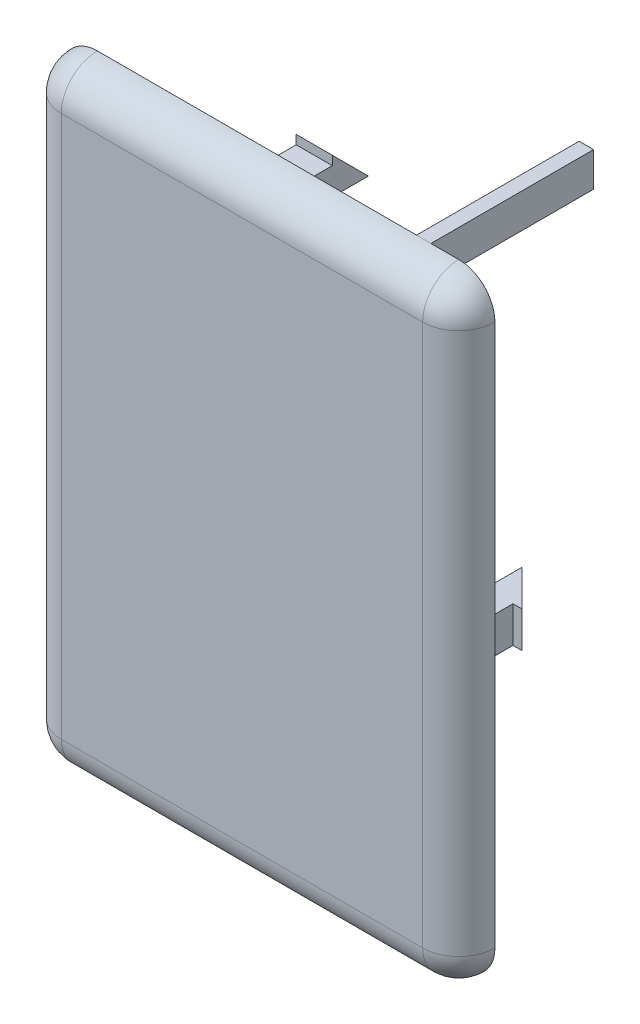
SolidWorks part; units mm, degrees
other "标注1"
sketch "草图6" plane through (-121.7901, 77.7286, -9) normal (-0.0529, 0.1135, -0.9921) x (-0.9984, 0.0112, 0.0545)
ref_plane "前视基准面" through (0, 0, 0) normal (0, 0, 1) x (1, 0, 0)
ref_plane "上视基准面" through (0, 0, 0) normal (0, 1, 0) x (1, 0, 0)
ref_plane "右视基准面" through (0, 0, 0) normal (1, 0, 0) x (0, 0, -1)
sketch "草图1" plane through (0, 0, 0) normal (0, 0, 1) x (1, 0, 0)
  line L1 (-97.7901, 77.7286) -> (-121.7901, 77.7286)
  line L2 (-97.7901, 77.7286) -> (-97.7901, 43.7286)
  line L3 (-97.7901, 43.7286) -> (-121.7901, 43.7286)
  line L4 (-121.7901, 77.7286) -> (-121.7901, 43.7286)
  dimension "D1" = 24
  dimension "D2" = 34
extrude "凸台-拉伸1" add sketch "草图1" along normal blind 2
sketch "草图3" plane through (0, 0, 0) normal (0, 0, -1) x (-1, 0, 0)
  line L1 (102.7901, 60.7286) -> (116.7901, 60.7286)
  line L2 (102.7901, 60.7286) -> (102.7901, 56.7286)
  line L3 (102.7901, 56.7286) -> (116.7901, 56.7286)
  line L4 (116.7901, 60.7286) -> (116.7901, 56.7286)
  line L6 (97.7901, 77.7286) -> (121.7901, 77.7286) construction
  line L7 (97.7901, 43.7286) -> (97.7901, 77.7286) construction
  line L8 (121.7901, 77.7286) -> (121.7901, 43.7286) construction
  dimension "D1" = 4
  dimension "D2" = 17
  dimension "D3" = 5
  dimension "D4" = 5
extrude "凸台-拉伸2" add sketch "草图3" along normal blind 4.8
fillet "圆角1" radius 2 4 edges at (-121.7901, 60.7286, 2) (-109.7901, 43.7286, 2) (-97.7901, 60.7286, 2) (-109.7901, 77.7286, 2)
sketch "草图4" plane through (0, 0, 0) normal (0, 0, -1) x (-1, 0, 0)
  line L0 (99.7901, 77.7286) -> (119.7901, 77.7286) construction
  line L2 (121.7901, 75.7286) -> (121.7901, 45.7286) construction
  circle A0 centre (117.4201, 68.2086) radius 1.05
  dimension "D1" = 9.52
  dimension "D3" = 2.1
  dimension "D2" = 4.37
extrude "切除-拉伸1" cut sketch "草图4" against normal blind 1
sketch "草图5" plane through (0, 0, 0) normal (0, 0, -1) x (-1, 0, 0)
  line L1 (101.3301, 77.7286) -> (102.1301, 77.7286)
  line L2 (101.3301, 77.7286) -> (101.3301, 75.8286)
  line L3 (101.3301, 75.8286) -> (102.1301, 75.8286)
  line L4 (102.1301, 77.7286) -> (102.1301, 75.8286)
  line L5 (99.7901, 77.7286) -> (119.7901, 77.7286) construction
  line L6 (97.7901, 45.7286) -> (97.7901, 75.7286) construction
  dimension "D1" = 0.8
  dimension "D2" = 3.54
  dimension "D3" = 1.9
extrude "凸台-拉伸3" add sketch "草图5" along normal blind 9 contours L2 L1 L4 L3
sketch "草图7" plane through (0, 0, 0) normal (0, 0, -1) x (-1, 0, 0)
  line L1 (99.2901, 57.7286) -> (101.2901, 57.7286)
  line L2 (99.2901, 57.7286) -> (99.2901, 59.7286)
  line L3 (99.2901, 59.7286) -> (101.2901, 59.7286)
  line L4 (101.2901, 57.7286) -> (101.2901, 59.7286)
  line L5 (97.7901, 45.7286) -> (97.7901, 75.7286) construction
  line L6 (118.2901, 57.7286) -> (120.2901, 57.7286)
  line L7 (118.2901, 57.7286) -> (118.2901, 59.7286)
  line L8 (118.2901, 59.7286) -> (120.2901, 59.7286)
  line L9 (120.2901, 57.7286) -> (120.2901, 59.7286)
  line L10 (109.7901, 74.2286) -> (111.7901, 74.2286)
  line L11 (109.7901, 74.2286) -> (109.7901, 76.2286)
  line L12 (109.7901, 76.2286) -> (111.7901, 76.2286)
  line L13 (111.7901, 74.2286) -> (111.7901, 76.2286)
  line L14 (121.7901, 75.7286) -> (121.7901, 45.7286) construction
  line L15 (102.1301, 77.7286) -> (119.7901, 77.7286) construction
  line L16 (119.7901, 43.7286) -> (99.7901, 43.7286) construction
  point P6 (89.5701, 32.2954)
  point P7 (108.7157, 59.9237)
  dimension "D1" = 2
  dimension "D2" = 2
  dimension "D3" = 1.5
  dimension "D4" = 2
  dimension "D5" = 2
  dimension "D6" = 2
  dimension "D7" = 2
  dimension "D8" = 1.5
  dimension "D9" = 1.5
  dimension "D10" = 10
  dimension "D11" = 14
extrude "凸台-拉伸4" add sketch "草图7" along normal blind 5
chamfer "倒角1" distance 2 angle 45 3 edges at (-110.7901, 76.2286, -5) (-120.2901, 58.7286, -5) (-99.2901, 58.7286, -5)
sketch "草图9" plane through (-99.2901, 0, 0) normal (1, 0, 0) x (0, 0, -1)
  line L1 (0, 57.7286) -> (3, 57.7286)
  line L2 (0, 57.7286) -> (0, 59.7286)
  line L3 (0, 59.7286) -> (3, 59.7286)
  line L4 (3, 57.7286) -> (3, 59.7286)
  point P4 (5.0736, 54.3249)
extrude "切除-拉伸2" cut sketch "草图9" against normal blind 0.5
sketch "草图10" plane through (-120.2901, 0, 0) normal (-1, 0, 0) x (0, 0, 1)
  line L1 (-3, 57.7286) -> (0, 57.7286)
  line L2 (-3, 57.7286) -> (-3, 59.7286)
  line L3 (-3, 59.7286) -> (0, 59.7286)
  line L4 (0, 57.7286) -> (0, 59.7286)
  point P4 (-3, 58.2286)
extrude "切除-拉伸4" cut sketch "草图10" against normal blind 0.5
sketch "草图11" plane through (0, 76.2286, 0) normal (0, 1, 0) x (1, 0, 0)
  line L1 (-109.7901, 0) -> (-111.7901, 0)
  line L2 (-109.7901, 0) -> (-109.7901, 3)
  line L3 (-109.7901, 3) -> (-111.7901, 3)
  line L4 (-111.7901, 0) -> (-111.7901, 3)
  point P4 (-110.8238, 2.5228)
extrude "切除-拉伸5" cut sketch "草图11" against normal blind 0.5
